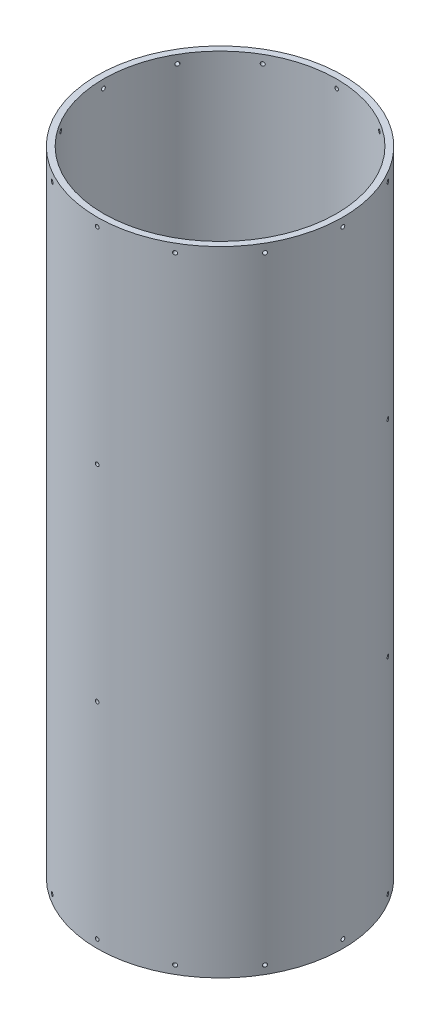
SolidWorks part; units mm, degrees
material "PVC Rigid"
ref_plane "Front Plane" through (0, 0, 0) normal (0, 0, 1) x (1, 0, 0)
ref_plane "Top Plane" through (0, 0, 0) normal (0, 1, 0) x (1, 0, 0)
ref_plane "Right Plane" through (0, 0, 0) normal (1, 0, 0) x (0, 0, -1)
sketch "Sketch1" plane through (0, 0, 0) normal (0, 1, 0) x (1, 0, 0)
  circle A0 centre (0, 0) radius 93.6625
  circle A1 centre (0, 0) radius 88.9
  dimension "D1" = 187.325
  dimension "D2" = 177.8
extrude "Boss-Extrude1" add sketch "Sketch1" along normal mid plane 482.854
ref_plane "Plane1" through (0, 0, 93.6625) normal (0, 0, 1) x (1, 0, 0)
sketch "Sketch3" plane through (0, 0, 93.6625) normal (0, 0, 1) x (1, 0, 0)
  line L0 (0, -55) -> (0, 55) construction
  line L1 (-93.6625, -241.427) -> (93.6625, -241.427) construction
  circle A0 centre (0, -235.077) radius 1.4351
  dimension "D1" = 2.8702
  dimension "D2" = 6.35
extrude "Cut-Extrude1" cut sketch "Sketch3" against normal blind 19.304
pattern_circular "CirPattern1" count 12 over 360 about axis through (0, 241.427, 0) along (0, -1, 0) of "Cut-Extrude1" reverse direction yes
mirror "Mirror1" about plane through (0, 0, 0) normal (0, 1, 0) of "CirPattern1", "Cut-Extrude1"
sketch "Sketch4" plane through (0, 0, 93.6625) normal (0, 0, 1) x (1, 0, 0)
  line L0 (0, -55) -> (0, 55) construction
  circle A0 centre (0, -78.359) radius 1.4351
  circle A1 centre (0, 78.359) radius 1.4351
  circle A2 centre (0, 235.077) radius 1.4351 construction
  circle A3 centre (0, -235.077) radius 1.4351 construction
  dimension "D1" = 2.8702
  dimension "D2" = 2.8702
  dimension "D3" = 156.718
  dimension "D4" = 156.718
extrude "Cut-Extrude2" cut sketch "Sketch4" against normal blind 25.146
pattern_circular "CirPattern2" count 3 over 360 about axis through (0, 241.427, 0) along (0, -1, 0) of "Cut-Extrude2"
